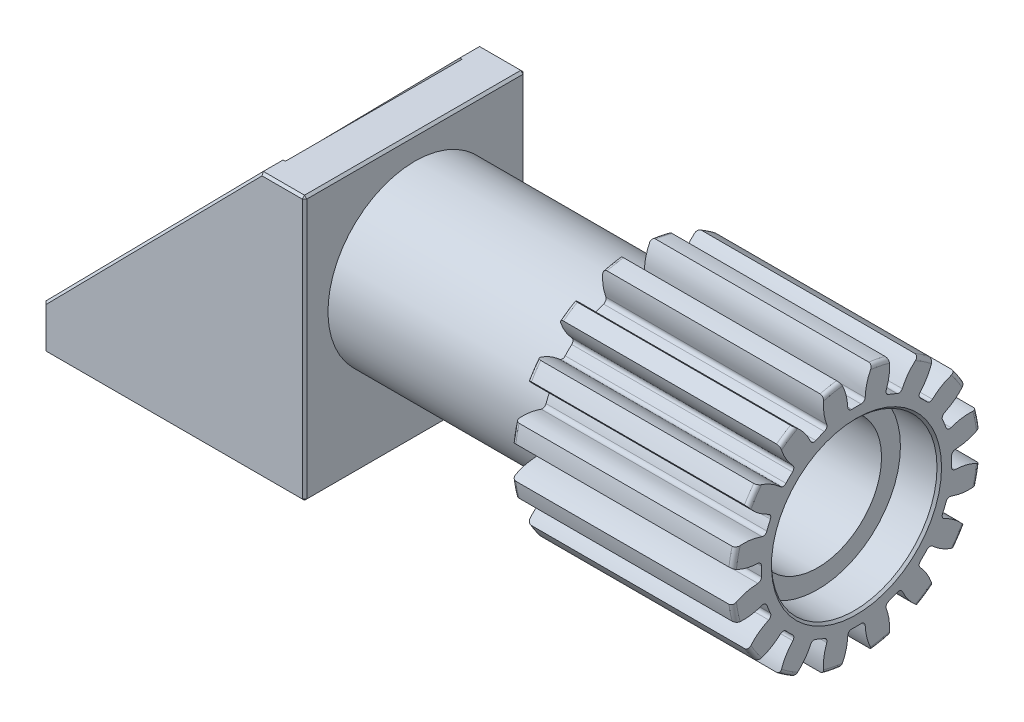
SolidWorks part; units mm, degrees
ref_plane "Front" through (0, 0, 0) normal (0, 0, 1) x (1, 0, 0)
ref_plane "Top" through (0, 0, 0) normal (0, 1, 0) x (1, 0, 0)
ref_plane "Right" through (0, 0, 0) normal (1, 0, 0) x (0, 0, -1)
sketch "Sketch1" plane through (0, 0, 0) normal (0, 0, 1) x (1, 0, 0)
  line L0 (-25.4, 0) -> (25.4, 0) construction
  line L1 (-25.4, 14.351) -> (0, 14.351)
  line L2 (-25.4, 14.351) -> (-25.4, 2)
  line L3 (-25.4, 2) -> (0, 2)
  line L8 (0, 14.351) -> (0, 2)
  dimension "OD" = 28.702
  dimension "For Shaft Diameter" = 4
  dimension "D2" = 25.4
sketch "Sketch2" plane through (0, 0, 0) normal (1, 0, 0) x (0, 0, -1)
  circle A0 centre (0, 0) radius 12.7
  circle A1 centre (0, 0) radius 2
  point P3 (8.9803, 8.9803)
  point P5 (11.7333, 4.8601)
  point P7 (0, -12.7)
  point P8 (-4.8601, -11.7333)
  point P9 (12.7, 0)
  point P10 (11.7333, -4.8601)
  point P11 (-8.9803, -8.9803)
  point P12 (-11.7333, -4.8601)
  point P13 (-12.7, 0)
  point P14 (-11.7333, 4.8601)
  point P15 (-8.9803, 8.9803)
  point P16 (-4.8601, 11.7333)
  point P17 (0, 12.7)
  point P18 (4.8601, 11.7333)
  point P19 (8.9803, -8.9803)
  point P20 (4.8601, -11.7333)
  point P26 (0, 0)
  dimension "Number of Teeth" = 16
sketch "Sketch12" plane through (0, 0, 0) normal (0, 0, 1) x (1, 0, 0)
  line L0 (-25.4, 14.351) -> (-25.4, 2) construction
  line L1 (-25.4, 14.351) -> (0, 14.351) construction
  line L5 (-25.4, 2) -> (0, 2) construction
  line L6 (-25.4, 14.351) -> (-25.4, 2)
  line L7 (-25.4, 14.351) -> (0, 14.351)
  line L11 (-25.4, 2) -> (0, 2)
  line L12 (0, 0) -> (25.4, 0) construction
  line L13 (0, 14.351) -> (0, 2) construction
  line L14 (0, 14.351) -> (0, 2)
revolve "Revolve3" add sketch "Sketch12" angle 360 about L12 region at (-12.7, 8.1755, 0)
sketch "Sketch6" plane through (-25.4, 0, 0) normal (-1, 0, 0) x (0, 0, -1)
  line L0 (-11.7799, 1.0374) -> (-12.651, 1.1141) construction
  line L1 (0, 0) -> (-10.9511, 0) construction
  line L2 (-12.651, 1.1141) -> (-17.3011, 3.2857) construction
  line L3 (0, 0) -> (-14.0752, -2.7997) construction
  line L4 (-17.3011, 3.2857) -> (-17.3011, -3.2857) construction
  line L5 (-17.3011, -3.2857) -> (-12.651, -1.1141) construction
  line L6 (-12.651, -1.1141) -> (-11.7799, -1.0374) construction
  line L7 (-10.9511, 0) -> (-14.351, 0) construction
  line L8 (-10.9089, -0.9607) -> (-10.9089, 0.9607) construction
  line L9 (-10.9089, -0.9607) -> (-11.7799, -1.0374)
  line L10 (-10.9089, 0.9607) -> (-11.7799, 1.0374)
  line L11 (-12.651, -1.1141) -> (-12.651, 1.1141) construction
  line L12 (-10.9089, -0.9607) -> (-12.651, -0.9607) construction
  circle A0 centre (0, 0) radius 12.7 construction
  circle A1 centre (0, 0) radius 10.9511 construction
  arc A2 (-10.9089, 0.9607) -> (-10.9089, -0.9607) centre (0, 0) ccw
  circle A4 centre (0, 0) radius 14.351 construction
  circle A6 centre (0, 0) radius 14.351 construction
  arc A7 (-13.8564, -3.735) -> (-14.231, -1.852) centre (0, 0) cw construction
  arc A8 (-14.231, -1.852) -> (-11.7799, -1.0374) centre (-11.2893, -6.6087) cw
  arc A9 (-11.7799, 1.0374) -> (-14.231, 1.852) centre (-11.2893, 6.6087) cw
  arc A10 (-14.231, 1.852) -> (-14.231, -1.852) centre (0, 0) ccw
  point P1 (-11.7799, -0.9607)
  point P7 (-12.651, 0)
  point P21 (-10.9089, -0.9607)
  point P24 (-10.9089, 0.9607)
  point P32 (-12.651, 0)
  dimension "D4" = 6.35
  dimension "D2" = 11.25
  dimension "D3" = 20
  dimension "D6" = 2.2282
sketch "Sketch7" plane through (0, 0, 0) normal (0, 0, 1) x (1, 0, 0)
  line L0 (-25.4, 0) -> (11.9126, 0)
  line L3 (-25.4, 0) -> (25.4, 0) construction
fillet "Fillet1" radius 0.4445 2 edges at (-25.4, -14.351, 0) (0, -14.351, 0)
sweep "Cut-Sweep1" cut profiles "Sketch6" path "Sketch7" parameters "D1"=0
fillet "Fillet2" radius 0.4456 2 edges
pattern_circular "CirPattern4" count 16 over 360 about axis through (-25.4, 0, 0) along (1, 0, 0) of "Cut-Sweep1", "Fillet2"
sketch "Sketch13" plane through (0, 0, 0) normal (1, 0, 0) x (0, 0, -1)
  circle A0 centre (0, 0) radius 10
  circle A1 centre (0, 7) radius 1.5
  circle A2 centre (7, 0) radius 1.5
  circle A3 centre (0, -7) radius 1.5
  circle A4 centre (-7, 0) radius 1.5
  point P14 (0, 0)
  dimension "D1" = 20
  dimension "D3" = 3
  dimension "D2" = 7
  dimension "D4" = 4
extrude "Boss-Extrude1" add sketch "Sketch13" against normal blind 25.4 from surface contours A0 starting at face at (-25.4, -2, 0)
sketch "Sketch15" plane through (0, 0, 0) normal (1, 0, 0) x (0, 0, -1)
  line L0 (12.7, -12.7) -> (12.7, -17.7)
  line L1 (12.7, 12.7) -> (-12.7, 12.7)
  line L2 (12.7, 12.7) -> (12.7, -12.7)
  line L3 (12.7, -12.7) -> (-12.7, -12.7)
  line L4 (-12.7, 12.7) -> (-12.7, -12.7)
  line L5 (12.7, 12.7) -> (-12.7, -12.7) construction
  line L6 (12.7, -12.7) -> (-12.7, 12.7) construction
  line L7 (12.7, -17.7) -> (-12.7, -17.7)
  line L8 (-12.7, -17.7) -> (-12.7, -12.7)
  point P0 (0, 0)
  dimension "D1" = 25.4
  dimension "D2" = 5
extrude "Boss-Extrude2" add sketch "Sketch15" against normal blind 5 from surface contours L1 L4 L3 L2 region at (0, 0, 0) starting at face at (-50.8, 10, 0)
extrude "Boss-Extrude3" add sketch "Sketch15<3>" against normal blind 30 from surface contours L8 L7 L0 L3 region at (0, -15.2, 0) starting at face at (-50.8, 10, 0)
sketch "Sketch15<3>" plane through (0, 0, 0) normal (1, 0, 0) x (0, 0, -1) same geometry as "Sketch15"
sketch "Sketch16" plane through (0, 0, 12.7) normal (0, 0, 1) x (1, 0, 0)
  line L0 (-80.8, -12.7) -> (-55.8, 12.7)
rib "Rib1" sketch "Sketch16" sketch "Sketch16" thickness 2.54 extrusion direction parallel to sketch draft on no parameters "D1"=2.54
sketch "Sketch17" plane through (0, 0, -12.7) normal (0, 0, -1) x (-1, 0, 0)
  line L0 (55.8, 12.7) -> (80.8, -12.7)
rib "Rib2" sketch "Sketch17" sketch "Sketch17" thickness 2.54 extrusion direction parallel to sketch draft on no parameters "D1"=2.54
sketch "Sketch18" plane through (0, 0, 0) normal (1, 0, 0) x (0, 0, -1)
  circle A0 centre (0, 0) radius 9.525
  circle A1 centre (0, 0) radius 7.35
  dimension "D1" = 19.05
  dimension "D2" = 14.7
extrude "Cut-Extrude1" cut sketch "Sketch18" against normal through all contours A1
extrude "Cut-Extrude2" cut sketch "Sketch18<3>" against normal blind 4.4688 contours A0
sketch "Sketch18<3>" plane through (0, 0, 0) normal (1, 0, 0) x (0, 0, -1) same geometry as "Sketch18"
extrude "Cut-Extrude3" cut sketch "Sketch18<4>" along normal blind 12.7 from surface contours A0 starting at face at (-55.8, -7.35, 0)
sketch "Sketch18<4>" plane through (0, 0, 0) normal (1, 0, 0) x (0, 0, -1) same geometry as "Sketch18"
chamfer "Chamfer1" distance 0.26 angle 45 17 edges at (-80.8, -17.7, 0) (-50.8, -17.7, 0) (-53.3, 12.7, -12.7) (-68.3, 0, -12.7) (-80.8, -15.2, -12.7) (-65.8, -17.7, -12.7) (-50.8, -2.5, -12.7) (-65.8, -17.7, 12.7) (-80.8, -15.2, 12.7) (-68.3, 0, 12.7) (-53.3, 12.7, 12.7) (-50.8, -2.5, 12.7) (-50.8, 12.7, 0) (-80.8, -12.7, 0) (-55.8, 12.7, 0) (0, 0, -9.525) (-55.8, -9.525, 0)
equation "\"D1@CirPattern4\" = \"Number of Teeth@Sketch2\""
equation "\"D1@Sketch2\" = \"For Shaft Diameter@Sketch1\""
equation "\"D2@Sketch6\" = 360 / \"Number of Teeth@Sketch2\" / 2"
equation "\"D1@Chamfer1\"=\"For Shaft Diameter@Sketch1\" * 0.065"
